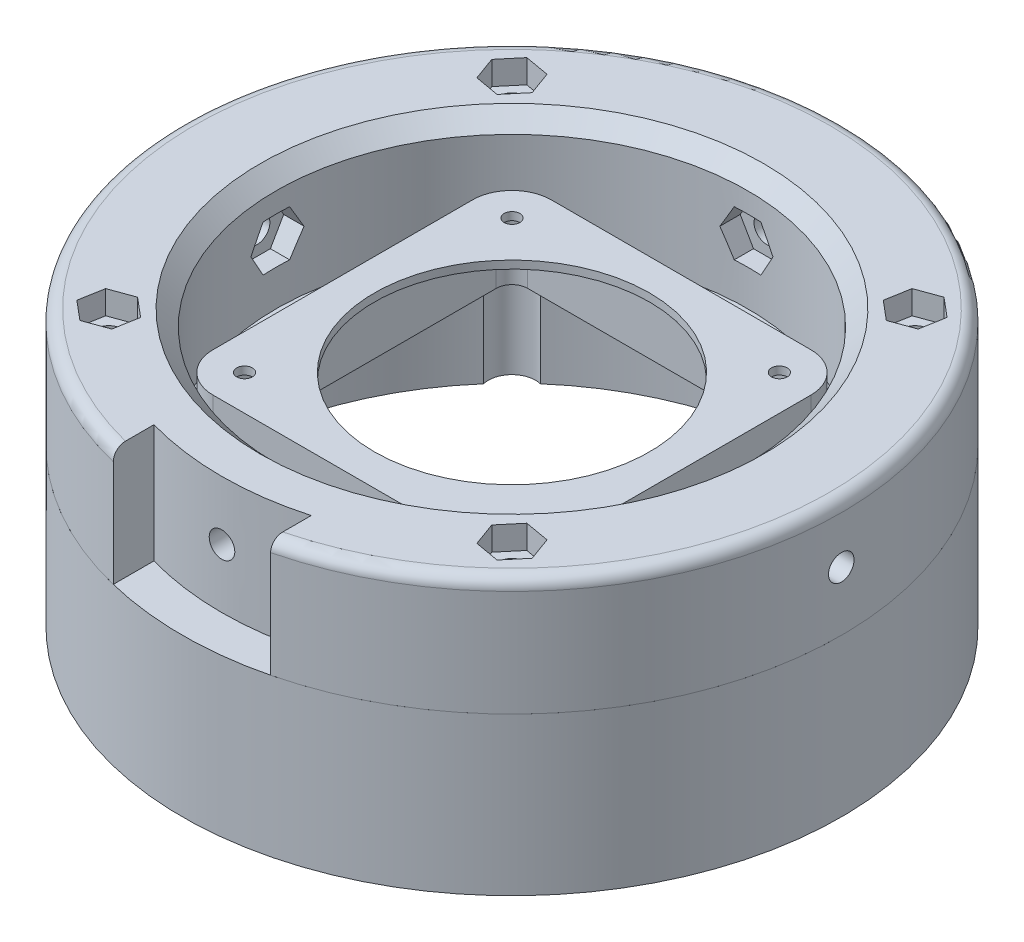
SolidWorks part; units mm, degrees
ref_plane "Front" through (0, 0, 0) normal (0, 0, 1) x (1, 0, 0)
ref_plane "Top" through (0, 0, 0) normal (0, 1, 0) x (1, 0, 0)
ref_plane "Right" through (0, 0, 0) normal (1, 0, 0) x (0, 0, -1)
sketch "Sketch1" plane through (0, 0, 0) normal (0, 1, 0) x (1, 0, 0)
  circle A0 centre (0, 0) radius 41.9
  dimension "D1" = 83.8
extrude "Top-Part" add sketch "Sketch1" along normal blind 15
sketch "Sketch2" plane through (0, 15, 0) normal (0, 1, 0) x (1, 0, 0)
  circle A0 centre (0, 0) radius 30
  dimension "D1" = 60
extrude "Cut-Extrude1" cut sketch "Sketch2" against normal blind 20
fillet "Fillet1" radius 1.5 1 edges at (0, 15, 41.9)
chamfer "Chamfer1" distance 2 angle 45 1 edges at (0, 15, 30)
sketch "Sketch8" plane through (0, 15, 0) normal (0, 1, 0) x (1, 0, 0)
  line L0 (0, 0) -> (0, 52.711) construction
  line L1 (25.0832, 22.5168) -> (28.0563, 23.5989)
  line L8 (0, 0) -> (-43.3951, 43.3951) construction
  line L9 (-25.6326, 25.6326) -> (-25.6326, 34.5059) construction
  line L10 (-22.5168, 25.0832) -> (-23.5989, 28.0563)
  line L11 (-23.5989, 28.0563) -> (-26.7147, 28.6057)
  line L12 (-26.7147, 28.6057) -> (-28.7485, 26.182)
  line L13 (-28.7485, 26.182) -> (-27.6663, 23.2089)
  line L14 (-27.6663, 23.2089) -> (-24.5505, 22.6595)
  line L15 (-24.5505, 22.6595) -> (-22.5168, 25.0832)
  line L16 (28.0563, 23.5989) -> (28.6057, 26.7147)
  line L17 (28.6057, 26.7147) -> (26.182, 28.7485)
  line L18 (26.182, 28.7485) -> (23.2089, 27.6663)
  line L19 (23.2089, 27.6663) -> (22.6595, 24.5505)
  line L20 (22.6595, 24.5505) -> (25.0832, 22.5168)
  line L21 (0, 0) -> (43.3951, 43.3951) construction
  line L23 (22.5168, -25.0832) -> (23.5989, -28.0563)
  line L24 (23.5989, -28.0563) -> (26.7147, -28.6057)
  line L25 (26.7147, -28.6057) -> (28.7485, -26.182)
  line L26 (28.7485, -26.182) -> (27.6663, -23.2089)
  line L27 (27.6663, -23.2089) -> (24.5505, -22.6595)
  line L28 (24.5505, -22.6595) -> (22.5168, -25.0832)
  line L29 (0, 0) -> (43.3951, -43.3951) construction
  line L31 (-25.0832, -22.5168) -> (-28.0563, -23.5989)
  line L32 (-28.0563, -23.5989) -> (-28.6057, -26.7147)
  line L33 (-28.6057, -26.7147) -> (-26.182, -28.7485)
  line L34 (-26.182, -28.7485) -> (-23.2089, -27.6663)
  line L35 (-23.2089, -27.6663) -> (-22.6595, -24.5505)
  line L36 (-22.6595, -24.5505) -> (-25.0832, -22.5168)
  line L37 (0, 0) -> (-43.3951, -43.3951) construction
  line L39 (-25.6326, 25.6326) -> (-27.9138, 12.6954) construction
  circle A0 centre (0, 0) radius 36.25 construction
  circle A1 centre (25.6326, 25.6326) radius 2.74 construction
  circle A2 centre (-25.6326, 25.6326) radius 2.74 construction
  circle A3 centre (25.6326, -25.6326) radius 2.74 construction
  circle A4 centre (-25.6326, -25.6326) radius 2.74 construction
  circle A5 centre (-25.6326, 25.6326) radius 1.625
  circle A6 centre (25.6326, 25.6326) radius 1.625
  circle A7 centre (25.6326, -25.6326) radius 1.625
  circle A8 centre (-25.6326, -25.6326) radius 1.625
  point P8 (25.6326, 25.6326)
  point P10 (28.331, 25.1568)
  point P18 (-25.6326, 25.6326)
  point P20 (-25.1568, 28.331)
  point P36 (25.6326, -25.6326)
  point P38 (25.1568, -28.331)
  point P50 (-25.6326, -25.6326)
  point P52 (-28.331, -25.1568)
  point P63 (0, 0)
  point P69 (-27.8231, 23.2366)
  dimension "D1" = 72.5
  dimension "D5" = 3.25
  dimension "D2" = 4
  dimension "D3" = 45
  dimension "D4" = 10
  dimension "D6" = 5.75
extrude "Cut-Extrude8" cut sketch "Sketch8<7>" against normal blind 3
sketch "Sketch8<7>" plane through (0, 15, 0) normal (0, 1, 0) x (1, 0, 0) same geometry as "Sketch8"
extrude "Cut-Extrude7" cut sketch "Sketch8" against normal through all contours A5 | A6 | A7 | A8
sketch "Sketch13" plane through (0, 0, 0) normal (0, -1, 0) x (1, 0, 0)
  line L0 (0, 0) -> (0, 66.0162) construction
  line L1 (-10, 35.5191) -> (-10, 40.6892)
  line L2 (10, 35.5191) -> (10, 40.6892)
  line L3 (-10, 40.6892) -> (10, 35.5191) construction
  line L4 (10, 40.6892) -> (-10, 35.5191) construction
  circle A0 centre (0, 0) radius 41.9 construction
  arc A1 (10, 40.6892) -> (-10, 40.6892) centre (0, 0) ccw
  arc A2 (10, 35.5191) -> (-10, 35.5191) centre (0, 0) ccw
  point P6 (0, 38.1042)
  point P10 (0, 36.9)
  point P12 (0, 41.9)
  dimension "D1" = 10
  dimension "D3" = 5
extrude "Cut-Extrude11" cut sketch "Sketch13" against normal through all
ref_plane "Plane2" through (0, 0, 41.9) normal (0, 0, 1) x (1, 0, 0)
ref_plane "Plane3" through (0, 0, 32.4) normal (0, 0, 1) x (1, 0, 0)
sketch "Sketch15" plane through (0, 0, 32.4) normal (0, 0, 1) x (1, 0, 0)
  line L0 (0, -23.0183) -> (0, 33.1182) construction
  circle A1 centre (0, 7.5) radius 1.625
  point P11 (0, 7.5)
  dimension "D3" = 3.25
  dimension "D1" = 7.5
extrude "Cut-Extrude14" cut sketch "Sketch15" against normal blind 10 and the other way blind 10
sketch "Sketch16" plane through (0, 0, 32.4) normal (0, 0, 1) x (1, 0, 0)
  line L0 (0, 0) -> (0, 26.985) construction
  line L2 (3.3775, 7.5) -> (1.6887, 10.425)
  line L3 (1.6887, 10.425) -> (-1.6887, 10.425)
  line L4 (-1.6887, 10.425) -> (-3.3775, 7.5)
  line L5 (-3.3775, 7.5) -> (-1.6887, 4.575)
  line L6 (-1.6887, 4.575) -> (1.6887, 4.575)
  line L7 (1.6887, 4.575) -> (3.3775, 7.5)
  circle A0 centre (0, 7.5) radius 2.925 construction
  point P4 (0, 4.575)
  point P13 (0, 10.425)
  dimension "D1" = 5.85
  dimension "D2" = 7.5
extrude "Cut-Extrude15" cut sketch "Sketch16" against normal blind 10
pattern_circular "CirPattern1" count 4 over 360 about axis through (0, 0, 0) along (0, 1, 0) of "Cut-Extrude14"
pattern_circular "CirPattern2" count 4 every 90 about axis through (0, 0, 0) along (0, 1, 0) of "Cut-Extrude15"
sketch "Sketch3" plane through (0, 0, 0) normal (0, -1, 0) x (1, 0, 0)
  circle A0 centre (0, 0) radius 41.9
  dimension "D1" = 83.8
extrude "Bottom-Part" add sketch "Sketch3" along normal blind 20 separate body
ref_plane "Plane1" through (0, -1.5, 0) normal (0, 1, 0) x (1, 0, 0)
sketch "Sketch6" plane through (0, -1.5, 0) normal (0, 1, 0) x (1, 0, 0)
  line L0 (0, 0) -> (-97.4577, 0) construction
  line L5 (-37.9, 0) -> (-41.9, 0) construction
  circle A0 centre (0, 0) radius 37.9
  circle A1 centre (0, 0) radius 41.9 construction
  circle A2 centre (0, 0) radius 41.9 construction
  point P6 (-37.9, 0)
  point P9 (-41.9, 0)
  dimension "D1" = 4
extrude "Cut-Extrude3" cut sketch "Sketch6" against normal through all
sketch "ｽｹｯﾁ1" plane through (0, 0, 0) normal (0, 1, 0) x (1, 0, 0)
  line L3 (21.5, -21.5) -> (-21.5, -21.5)
  line L4 (21.5, -21.5) -> (21.5, 21.5)
  line L5 (21.5, 21.5) -> (-21.5, 21.5)
  line L6 (-21.5, -21.5) -> (-21.5, 21.5)
  line L7 (21.5, -21.5) -> (-21.5, 21.5) construction
  line L8 (21.5, 21.5) -> (-21.5, -21.5) construction
  point P2 (0, 0)
  dimension "D1" = 43
extrude "ﾎﾞｽ - 押し出し1" add sketch "ｽｹｯﾁ1" along normal blind 8
fillet "ﾌｨﾚｯﾄ1" radius 5 4 edges at (21.5, 4, -21.5) (-21.5, 4, -21.5) (-21.5, 4, 21.5) (21.5, 4, 21.5)
sketch "Sketch7" plane through (0, -1.5, 0) normal (0, 1, 0) x (1, 0, 0)
  circle A0 centre (0, 0) radius 17.5
  circle A1 centre (17, -17) radius 1
  circle A2 centre (-17, -17) radius 1
  circle A3 centre (-17, 17) radius 1
  circle A4 centre (17, 17) radius 1
  dimension "D1" = 35
  dimension "D2" = 2
extrude "Cut-Extrude4" cut sketch "Sketch7" against normal through all and the other way through all
sketch "Sketch12" plane through (0, -1.5, 0) normal (0, -1, 0) x (1, 0, 0)
  line L1 (19.75, -19.75) -> (-19.75, -19.75)
  line L2 (19.75, -19.75) -> (19.75, 19.75)
  line L3 (19.75, 19.75) -> (-19.75, 19.75)
  line L4 (-19.75, -19.75) -> (-19.75, 19.75)
  line L5 (19.75, -19.75) -> (-19.75, 19.75) construction
  line L6 (19.75, 19.75) -> (-19.75, -19.75) construction
  point P0 (0, 0)
  dimension "D1" = 39.5
extrude "Cut-Extrude10" cut sketch "Sketch12" against normal blind 8.5
fillet "Fillet3" radius 2 4 edges at (-19.75, 2.75, -19.75) (-19.75, 2.75, 19.75) (19.75, 2.75, -19.75) (19.75, 2.75, 19.75)
sketch "Sketch17" plane through (0, -1.5, 0) normal (0, -1, 0) x (1, 0, 0)
  circle A0 centre (25.6326, -25.6326) radius 1.625 construction
  circle A1 centre (-25.6326, -25.6326) radius 1.625 construction
  circle A2 centre (25.6326, 25.6326) radius 1.625 construction
  circle A3 centre (-25.6326, 25.6326) radius 1.625 construction
  circle A4 centre (25.6326, -25.6326) radius 1.625
  circle A5 centre (-25.6326, -25.6326) radius 1.625
  circle A6 centre (25.6326, 25.6326) radius 1.625
  circle A7 centre (-25.6326, 25.6326) radius 1.625
extrude "Cut-Extrude16" cut sketch "Sketch17" against normal through all
sketch "Sketch18" plane through (0, -1.5, 0) normal (0, -1, 0) x (1, 0, 0)
  circle A0 centre (-25.6326, 25.6326) radius 3
  circle A1 centre (25.6326, 25.6326) radius 3
  circle A2 centre (25.6326, -25.6326) radius 3
  circle A3 centre (-25.6326, -25.6326) radius 3
  dimension "D1" = 6
extrude "Cut-Extrude17" cut sketch "Sketch18" along normal through all
